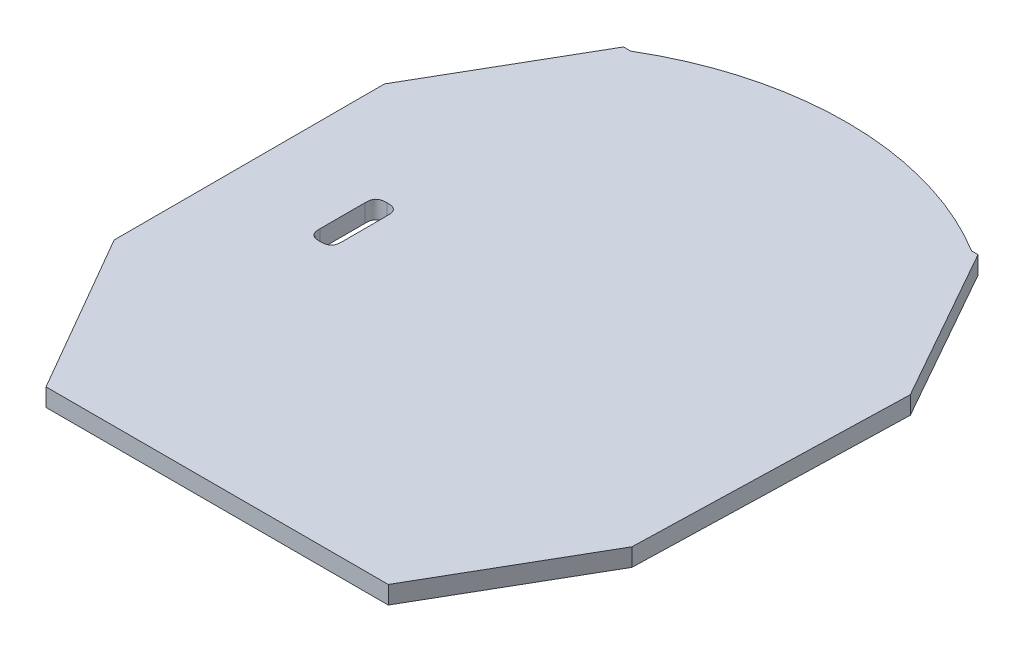
SolidWorks part; units mm, degrees
ref_plane "Front Plane" through (0, 0, 0) normal (0, 0, 1) x (1, 0, 0)
ref_plane "Top Plane" through (0, 0, 0) normal (0, 1, 0) x (1, 0, 0)
ref_plane "Right Plane" through (0, 0, 0) normal (1, 0, 0) x (0, 0, -1)
sketch "Sketch2" plane through (0, 0, 0) normal (0, 1, 0) x (1, 0, 0)
  line L0 (-113.5267, -19.5043) -> (-115.5267, -19.5043)
  line L1 (-115.5267, -19.5043) -> (-115.5267, -25.5043)
  line L2 (-123.8767, -10.3934) -> (-123.8767, -34.6153)
  line L3 (-123.8767, -34.6153) -> (-115.5329, -49.0671)
  line L4 (-115.5267, -25.5043) -> (-113.5267, -25.5043)
  line L6 (-113.5267, -19.5043) -> (-113.5267, -25.5043)
  line L14 (-115.5329, -49.0671) -> (-84.8608, -49.0671)
  line L15 (-84.8608, -49.0671) -> (-76.867, -35.2214)
  line L16 (-76.867, -35.2214) -> (-76.199, -10.944)
  line L17 (-84.0334, 2.9523) -> (-76.199, -10.944)
  line L18 (-84.616, 2.9566) -> (-84.0334, 2.9523)
  line L19 (-116.0357, 3.1876) -> (-115.4018, 3.1829)
  line L20 (-123.8767, -10.3934) -> (-116.0357, 3.1876)
  arc A2 (-115.4018, 3.1829) -> (-84.616, 2.9566) centre (-100.1969, -22.5043) cw
extrude "Boss-Extrude1" add sketch "Sketch2" along normal blind 1.6
fillet "Fillet1" radius 1 4 edges at (-113.5267, 0.8, 25.5043) (-115.5267, 0.8, 25.5043) (-113.5267, 0.8, 19.5043) (-115.5267, 0.8, 19.5043) curvature continuous yes
